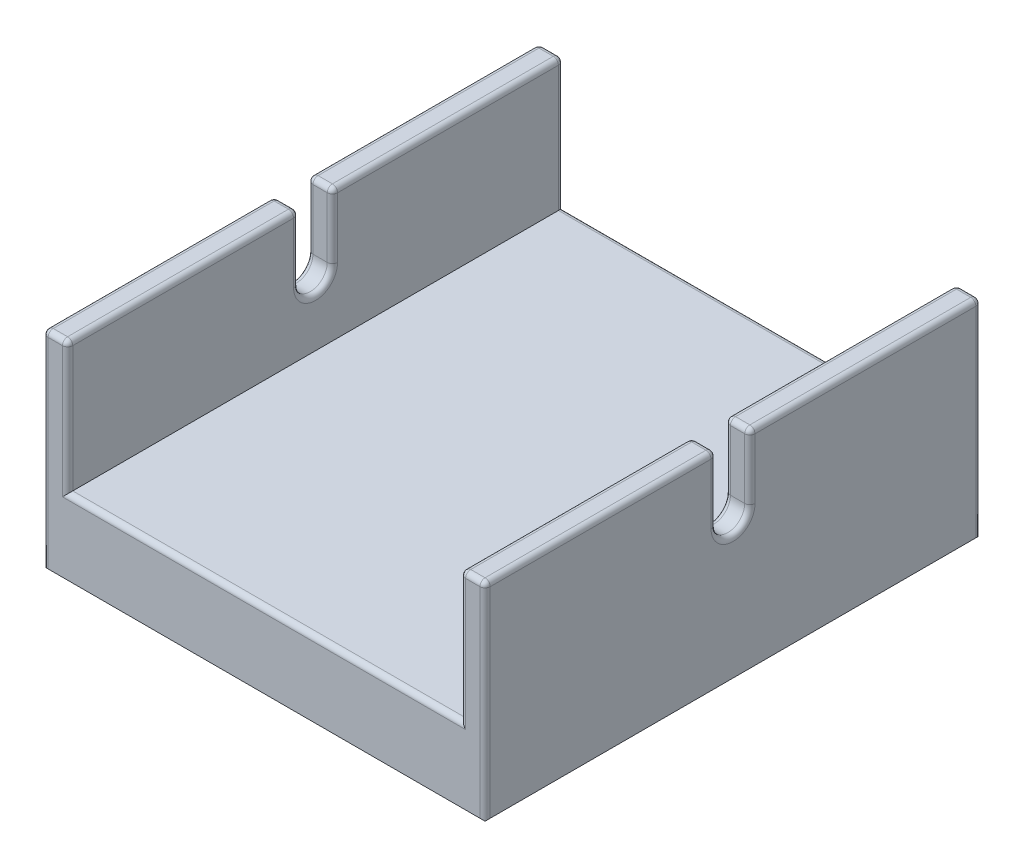
SolidWorks part; units mm, degrees
material "ABS"
ref_plane "Front Plane" through (0, 0, 0) normal (0, 0, 1) x (1, 0, 0)
ref_plane "Top Plane" through (0, 0, 0) normal (0, 1, 0) x (1, 0, 0)
ref_plane "Right Plane" through (0, 0, 0) normal (1, 0, 0) x (0, 0, -1)
sketch "Sketch2" plane through (0, 34, 0) normal (0, -1, 0) x (-1, 0, 0)
  line L0 (-150, -197.8) -> (-150, 107) construction
  line L1 (-152.164, -197.8) -> (-147.836, -197.8) construction
  line L2 (-300, 107) -> (0, 107) construction
  line L4 (-107.1248, 0) -> (-192.8752, 0)
  line L5 (-107.1248, 0) -> (-107.1248, -96.2)
  line L6 (-107.1248, -96.2) -> (-192.8752, -96.2)
  line L7 (-192.8752, 0) -> (-192.8752, -96.2)
  line L8 (-107.1248, 0) -> (-192.8752, -96.2) construction
  line L9 (-107.1248, -96.2) -> (-192.8752, 0) construction
  line L10 (-300, 0) -> (0, 0) construction
  line L11 (-188.1, -96.2) -> (-188.1, 0)
  line L12 (-111.9, -96.2) -> (-111.9, 0)
  line L13 (-107.1248, -10) -> (-192.8752, -10)
  point P6 (-150, -48.1)
  dimension "D1" = 10
extrude "Boss-Extrude1" add sketch "Sketch2" along normal blind 15 contours L6 L7 L4 L5
extrude "Boss-Extrude2" add sketch "Sketch2<3>" against normal blind 25.4 contours L5 L13 L12 L6 | L13 L5 L4 L12 | L11 L13 L7 L6 | L13 L11 L4 L7 region at (109.5124, 34, 5) region at (109.5124, 34, 53.1) region at (190.4876, 34, 5) region at (190.4876, 34, 53.1)
sketch "Sketch2<3>" plane through (0, 34, 0) normal (0, -1, 0) x (-1, 0, 0) same geometry as "Sketch2"
sketch "Sketch3" plane through (192.8752, 0, 0) normal (1, 0, 0) x (0, 0, -1)
  line L0 (107, 46.7) -> (-96.2, 46.7) construction
  line L1 (107, 48.864) -> (107, 44.536) construction
  line L2 (-96.2, 19) -> (-96.2, 59.4) construction
  line L3 (-51.3639, 46.7) -> (-51.3639, 59.4)
  line L4 (-51.3639, 59.4) -> (-44.8361, 59.4)
  line L5 (-44.8361, 59.4) -> (-44.8361, 46.7)
  line L6 (0, 59.4) -> (-96.2, 59.4) construction
  line L7 (-51.3639, 59.4) -> (-96.2, 59.4) construction
  line L8 (-44.8361, 59.4) -> (0, 59.4) construction
  arc A0 (-44.8361, 46.7) -> (-51.3639, 46.7) centre (-48.1, 46.7) cw
  dimension "D1" = 3.2639
extrude "Cut-Extrude1" cut sketch "Sketch3" against normal through all
chamfer "Chamfer1" distance 0.5 angle 45 4 edges at (150, 19, 96.2) (192.8752, 19, 48.1) (150, 19, 0) (107.1248, 19, 48.1)
fillet "Fillet2" radius 1 38 edges at (111.9, 53.05, 44.8361) (111.9, 43.4361, 48.1) (107.1248, 53.05, 44.8361) (107.1248, 43.4361, 48.1) (192.8752, 53.05, 44.8361) (192.8752, 43.4361, 48.1) (188.1, 53.05, 44.8361) (188.1, 43.4361, 48.1) (109.5124, 59.4, 0) (111.9, 59.4, 22.4181) (109.5124, 59.4, 44.8361) (107.1248, 59.4, 22.4181) (109.5124, 59.4, 96.2) (107.1248, 59.4, 73.782) (111.9, 59.4, 73.782) (190.4876, 59.4, 0) (192.8752, 59.4, 22.4181) (190.4876, 59.4, 44.8361) (188.1, 59.4, 22.4181) (190.4876, 59.4, 96.2) (188.1, 59.4, 73.782) (192.8752, 59.4, 73.782) (111.9, 53.05, 51.3639) (109.5124, 59.4, 51.3639) (107.1248, 53.05, 51.3639) (192.8752, 53.05, 51.3639) (190.4876, 59.4, 51.3639) (188.1, 53.05, 51.3639) (150, 34, 96.2) (107.1248, 39.45, 96.2) (188.1, 46.7, 96.2) (111.9, 46.7, 96.2) (192.8752, 39.45, 96.2) (107.1248, 39.45, 0) (192.8752, 39.45, 0) (188.1, 46.7, 0) (150, 34, 0) (111.9, 46.7, 0)
